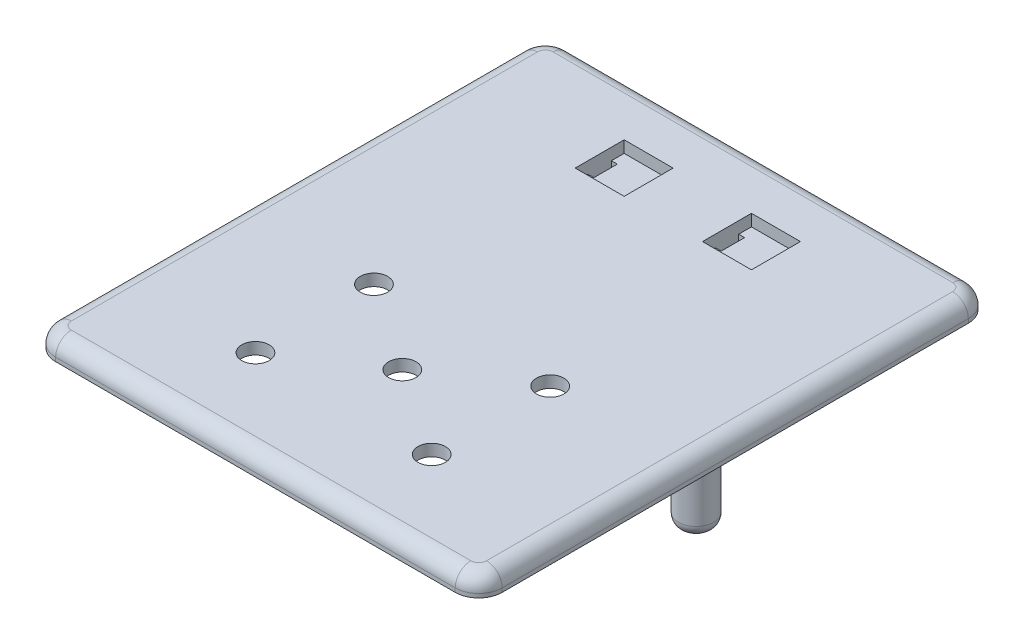
SolidWorks part; units mm, degrees
ref_plane "Front Plane" through (0, 0, 0) normal (0, 0, 1) x (1, 0, 0)
ref_plane "Top Plane" through (0, 0, 0) normal (0, 1, 0) x (1, 0, 0)
ref_plane "Right Plane" through (0, 0, 0) normal (1, 0, 0) x (0, 0, -1)
sketch "Sketch1" plane through (0, 0, 0) normal (0, 1, 0) x (1, 0, 0)
  line L1 (-57, -65.5) -> (57, -65.5)
  line L2 (-57, -65.5) -> (-57, 65.5)
  line L3 (-57, 65.5) -> (57, 65.5)
  line L4 (57, -65.5) -> (57, 65.5)
  line L5 (-57, -65.5) -> (57, 65.5) construction
  line L6 (-57, 65.5) -> (57, -65.5) construction
  point P0 (0, 0)
  point P6 (57, 4.5)
  point P7 (57, -0.5)
  point P8 (2466.975, 212.5266)
  point P9 (57, -25.5)
  point P10 (57, -984.6473)
  point P11 (57, -1284.6848)
  point P12 (57, -1468.0411)
  point P13 (52, 65.5)
  point P14 (-52, 65.5)
  point P15 (-42, 65.5)
  point P16 (42, 65.5)
  point P17 (57, -55.5)
  point P18 (57, -65.5)
  point P21 (57, 60.5)
  point P22 (57, -30.5)
  dimension "D1" = 84
  dimension "D2" = 5
  dimension "D3" = 5
  dimension "D4" = 10
  dimension "D5" = 10
  dimension "D7" = 5
  dimension "D8" = 25
  dimension "D9" = 5
  dimension "D10" = 25
  dimension "D11" = 10
  dimension "D12" = 10
  dimension "D6" = 5
  dimension "D13" = 56
extrude "Boss-Extrude1" add sketch "Sketch1" along normal blind 5
sketch "Sketch3" plane through (0, 0, 0) normal (0, -1, 0) x (1, 0, 0)
  line L0 (52, -60.5) -> (52, 60.5)
  line L1 (52, 60.5) -> (-52, 60.5)
  line L2 (-52, 60.5) -> (-52, -60.5)
  line L3 (-52, -60.5) -> (52, -60.5)
  line L4 (57, -65.5) -> (57, 65.5)
  line L5 (57, 65.5) -> (-57, 65.5)
  line L6 (-57, 65.5) -> (-57, -65.5)
  line L7 (-57, -65.5) -> (57, -65.5)
  line L8 (57, -65.5) -> (57, 65.5)
  line L9 (57, 65.5) -> (-57, 65.5)
  line L10 (-57, 65.5) -> (-57, -65.5)
  line L11 (-57, -65.5) -> (57, -65.5)
  dimension "D1" = 0
  dimension "D2" = 5
extrude "Cut-Extrude2" cut sketch "Sketch3" against normal offset from surface (2 mm away) 3 contours L0 L1 L2 L3 up to face at (0, 5, 0)
fillet "Fillet1" radius 6 4 edges at (-57, 2.5, 65.5) (-57, 2.5, -65.5) (57, 2.5, -65.5) (57, 2.5, 65.5)
fillet "Fillet2" radius 4 8 edges at (-55.2426, 5, -63.7426) (0, 5, -65.5) (55.2426, 5, -63.7426) (57, 5, 0) (55.2426, 5, 63.7426) (0, 5, 65.5) (-55.2426, 5, 63.7426) (-57, 5, 0)
fillet "Fillet3" radius 6 4 edges at (-52, 1, 60.5) (-52, 1, -60.5) (52, 1, 60.5) (52, 1, -60.5)
sketch "Sketch5" plane through (0, 0, 0) normal (0, -1, 0) x (1, 0, 0)
  line L0 (-52, 0) -> (-57, 0) construction
  line L1 (-52, -54.5) -> (-52, 54.5) construction
  line L2 (-57, -59.5) -> (-57, 59.5) construction
  line L3 (0, -13.75) -> (0, 13.75) construction
  line L4 (52, 0) -> (57, 0) construction
  circle A0 centre (-47, 0) radius 7.5
  circle A1 centre (47, 0) radius 7.5
  point P8 (-54.5, 0)
  point P10 (-54.5, 0)
  point P12 (-47, 0)
  point P17 (47, 0)
  point P18 (54.5, 0)
  dimension "D1" = 15
extrude "Boss-Extrude2" add sketch "Sketch5" against normal up to surface (2 mm away) up to face at (0, 2, 0)
fillet "Fillet4" radius 6 2 edges at (-52, 1, 5.5902) (-52, 1, -5.5902)
fillet "Fillet7" radius 6 2 edges at (52, 1, 5.5902) (52, 1, -5.5902)
sketch "Sketch15" plane through (0, 0, 0) normal (0, -1, 0) x (1, 0, 0)
  circle A0 centre (-47, 0) radius 4.5
  circle A1 centre (47, 0) radius 4.5
  dimension "D1" = 9
  dimension "D2" = 9
extrude "Boss-Extrude4" add sketch "Sketch15" along normal blind 20
fillet "Fillet8" radius 3 2 edges at (47, -20, -4.5) (-47, -20, -4.5)
sketch "Sketch10" plane through (0, 0, 0) normal (0, 1, 0) x (1, 0, 0)
  line L4 (53, -59.5) -> (53, 59.5)
  line L5 (-51, -61.5) -> (51, -61.5)
  line L6 (-53, 59.5) -> (-53, -59.5)
  line L7 (51, 61.5) -> (-51, 61.5)
  line L8 (53, -59.5) -> (53, 59.5)
  line L9 (-51, -61.5) -> (51, -61.5)
  line L10 (-53, 59.5) -> (-53, -59.5)
  line L11 (51, 61.5) -> (-51, 61.5)
  line L12 (0, -25.5) -> (0, -30.5) construction
  circle A1 centre (-22.5, -43) radius 3.5
  circle A2 centre (-22.5, -43) radius 3.5
  circle A3 centre (22.5, -43) radius 3.5
  circle A4 centre (22.5, -43) radius 3.5
  circle A5 centre (22.5, -12.7493) radius 3.5
  circle A6 centre (22.5, -12.7493) radius 3.5
  circle A7 centre (-22.5, -12.7493) radius 3.5
  circle A8 centre (-22.5, -12.7493) radius 3.5
  arc A12 (51, -61.5) -> (53, -59.5) centre (51, -59.5) ccw
  arc A13 (-53, -59.5) -> (-51, -61.5) centre (-51, -59.5) ccw
  arc A14 (-51, 61.5) -> (-53, 59.5) centre (-51, 59.5) ccw
  arc A15 (53, 59.5) -> (51, 61.5) centre (51, 59.5) ccw
  arc A16 (51, -61.5) -> (53, -59.5) centre (51, -59.5) ccw
  arc A17 (-53, -59.5) -> (-51, -61.5) centre (-51, -59.5) ccw
  arc A18 (-51, 61.5) -> (-53, 59.5) centre (-51, 59.5) ccw
  arc A19 (53, 59.5) -> (51, 61.5) centre (51, 59.5) ccw
  circle A24 centre (0, -28) radius 3.5
  dimension "D1" = 0
  dimension "D2" = 0
  dimension "D3" = 0
  dimension "D4" = 0
  dimension "D5" = 0
extrude "Cut-Extrude3" cut sketch "Sketch10" along normal through all contours A6 | A4 | A2 | A8 | A24
sketch "Sketch11" plane through (0, 5, 0) normal (0, 1, 0) x (1, 0, 0)
  line L0 (0, 84.2173) -> (0, -80.3563) construction
  line L1 (-22.5, 51.1335) -> (-10, 38.6335) construction
  line L2 (-22.5, 51.1335) -> (-10, 51.1335)
  line L3 (-22.5, 51.1335) -> (-22.5, 38.6335)
  line L4 (-22.5, 38.6335) -> (-10, 38.6335)
  line L5 (-10, 51.1335) -> (-10, 38.6335)
  line L6 (-27.5, 33.6335) -> (-5, 33.6335)
  line L7 (-5, 56.1335) -> (-5, 33.6335)
  line L8 (-27.5, 56.1335) -> (-5, 56.1335)
  line L9 (-27.5, 56.1335) -> (-27.5, 33.6335)
  dimension "D1" = 12.5
  dimension "D2" = 12.5
  dimension "D3" = 10
  dimension "D4" = 5
extrude "Boss-Extrude3" add sketch "Sketch11" against normal blind 8 contours L8 L9 L6 L7 L2 L5 L4 L3 | L5 L2 L3 L4 region at (-16.25, 5, -44.8835) region at (-27.1818, 5, -44.8835)
sketch "Sketch13" plane through (0, 5, 0) normal (0, 1, 0) x (1, 0, 0)
  line L1 (-22.5, 51.1335) -> (-22.5, 38.6335) construction
  line L2 (-22.5, 51.1335) -> (-10, 51.1335) construction
  line L3 (-10, 51.1335) -> (-10, 38.6335) construction
  line L4 (-22.5, 38.6335) -> (-10, 38.6335) construction
  line L6 (-22.5, 51.1335) -> (-22.5, 38.6335)
  line L7 (-22.5, 51.1335) -> (-10, 51.1335)
  line L8 (-10, 51.1335) -> (-10, 38.6335)
  line L9 (-22.5, 38.6335) -> (-10, 38.6335)
extrude "Cut-Extrude5" cut sketch "Sketch13" against normal blind 3 and the other way through all
sketch "Sketch14" plane through (0, 2, 0) normal (0, 1, 0) x (1, 0, 0)
  line L0 (-27.5, 44.8835) -> (-5, 44.8835) construction
  line L1 (-27.5, 56.1335) -> (-27.5, 33.6335) construction
  line L2 (-5, 56.1335) -> (-5, 33.6335) construction
  line L3 (-22.5, 51.1335) -> (-22.5, 38.6335) construction
  line L4 (-22.5, 47.8835) -> (-21, 47.8835)
  line L5 (-22.5, 47.8835) -> (-22.5, 41.8835)
  line L6 (-22.5, 41.8835) -> (-21, 41.8835)
  line L7 (-21, 47.8835) -> (-21, 41.8835)
  line L8 (-16.25, 56.1335) -> (-16.25, 33.6335) construction
  line L9 (-27.5, 56.1335) -> (-5, 56.1335) construction
  line L10 (-27.5, 33.6335) -> (-5, 33.6335) construction
  line L11 (-10, 41.8835) -> (-11.5, 41.8835)
  line L12 (-11.5, 47.8835) -> (-11.5, 41.8835)
  line L13 (-10, 47.8835) -> (-11.5, 47.8835)
  line L14 (-10, 47.8835) -> (-10, 41.8835)
  point P12 (-22.5, 44.8835)
  dimension "D1" = 6
  dimension "D2" = 1.5
extrude "Cut-Extrude6" cut sketch "Sketch14" against normal through all both and the other way through all
fillet "Fillet10" radius 5 4 edges at (-16.25, 2, -33.6335) (-16.25, 2, -56.1335) (-5, 2, -44.8835) (-27.5, 2, -44.8835)
mirror "Mirror1" about plane through (0, 0, 0) normal (1, 0, 0) of "Fillet10", "Cut-Extrude6", "Cut-Extrude5", "Boss-Extrude3"
sketch "Sketch16" plane through (0, 2, 0) normal (0, -1, 0) x (1, 0, 0)
  line L3 (0, -84.2173) -> (0, 80.3563) construction
  line L4 (0, -84.2173) -> (0, 80.3563) construction
  line L8 (-11.8797, 0) -> (11.8797, 0)
  line B0 (-11.8797, 0) -> (-11.8797, -11.3723)
  line B1 (-11.8797, -11.3723) -> (-6.1936, -5.6862)
  line B2 (-6.1936, -5.6862) -> (0, -11.8797)
  line B3 (6.1936, -5.6862) -> (0, -11.8797)
  line B4 (11.8797, -11.3723) -> (6.1936, -5.6862)
  line B5 (11.8797, 0) -> (11.8797, -11.3723)
sketch_block_instance "Block1-1"
sketch_block "Block1"
extrude "Cut-Extrude7" cut sketch "Sketch16" against normal blind 1 contours L4 B3 B4 B5 L8 | B2 L4 L8 B0 B1 region at (-5.8529, 2, -4.5023) region at (5.8529, 2, -4.5023)
equation "\"breadboard_width\"= 84"
equation "\"allowance1\"=5"
equation "\"base_thickness\"= 395.05"
equation "\"pot_length\"= 25"
equation "\"breadboard_length\"= 56"
equation "\"allowance2\"=10"
equation "\"base_thckness\"=5"
equation "\"breadboard_height\"= 9.5"
equation "\"allowance3\"=14.5"
equation "\"fillet1\"=6"
equation "\"screw_outer1\"= 15"
equation "\"battery_tray_height\"= 19.5"
equation "\"battery_tray_length\" =76"
equation "\"battery_tray_width\"=42"
equation "\"bms_width\"= 17.6"
equation "\"bms_height\"= 55"
equation "\"barrel_jack_height\"= 11.7"
equation "\"pot_pot\"=12"
equation "\"allowance4\" = 2"
equation "\"D1@Sketch1\"=\"breadboard_width\""
equation "\"D7@Sketch1\"=\"allowance1\""
equation "\"D9@Sketch1\"=\"allowance1\""
equation "\"D10@Sketch1\"=\"pot_length\""
equation "\"D12@Sketch1\"=\"allowance2\""
equation "\"D6@Sketch1\"=\"base_thckness\""
equation "\"D13@Sketch1\"=\"breadboard_length\""
equation "\"D1@Sketch5\"=\"screw_outer1\""
equation "\"screw\"=9"
equation "\"D2@Sketch15\"=\"screw\""
equation "\"D1@Sketch15\"=\"screw\""
